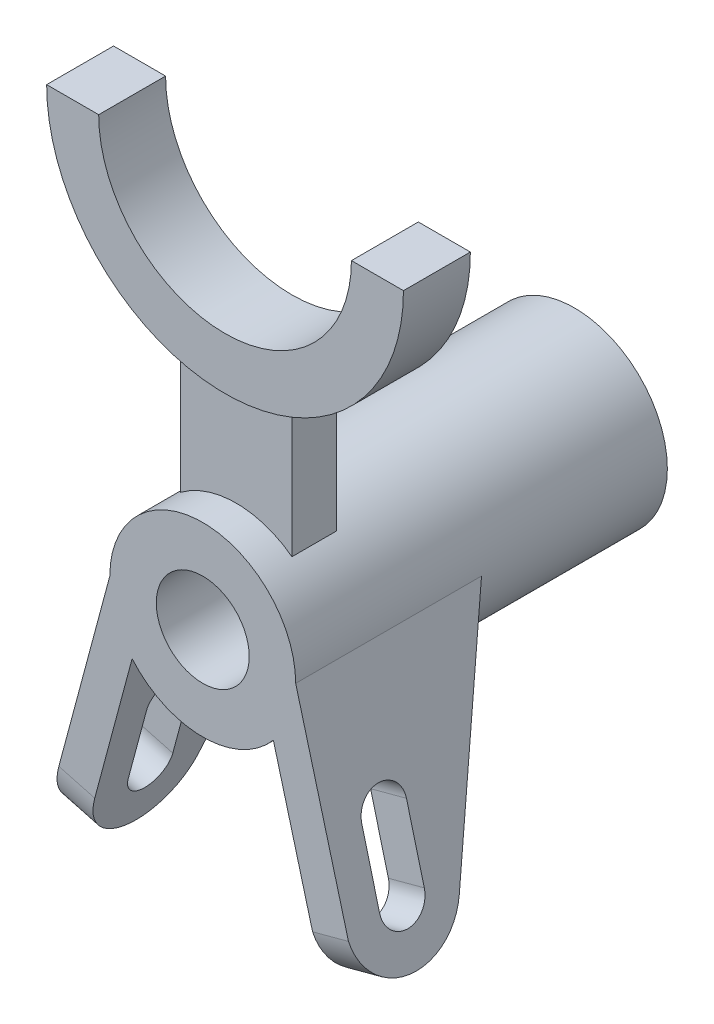
SolidWorks part; units mm, degrees
note: The reader was unsure of these and kept them because the rebuilt part matched: shared geometry of "Sketch1<3>", "Sketch1<4>", "Sketch1<5>", "Sketch1<6>".
material "텅스텐"
ref_plane "정면" through (0, 0, 0) normal (0, 0, 1) x (1, 0, 0)
ref_plane "윗면" through (0, 0, 0) normal (0, 1, 0) x (1, 0, 0)
ref_plane "우측면" through (0, 0, 0) normal (1, 0, 0) x (0, 0, -1)
sketch "Sketch1" plane through (0, 0, 0) normal (0, 0, 1) x (1, 0, 0)
  line L0 (-48, 100) -> (-34, 100)
  line L1 (34, 100) -> (48, 100)
  line L2 (0, -80.5181) -> (0, 148.3277) construction
  line L5 (-15, 20) -> (-15, 57.4935)
  line L7 (15, 20) -> (15, 57.4935)
  line L8 (25, 0) -> (42.5997, -65.683)
  line L9 (42.5997, -65.683) -> (32.9404, -68.2711)
  line L10 (32.9404, -68.2711) -> (15.3407, -2.5882)
  line L11 (15.3407, -2.5882) -> (25, 0)
  line L12 (-32.9404, -68.2711) -> (-15.3407, -2.5882)
  line L13 (-42.5997, -65.683) -> (-32.9404, -68.2711)
  line L14 (-25, 0) -> (-42.5997, -65.683)
  line L15 (-15.3407, -2.5882) -> (-25, 0)
  circle A0 centre (0, 0) radius 25
  arc A1 (-48, 100) -> (48, 100) centre (0, 100) ccw
  arc A3 (-34, 100) -> (34, 100) centre (0, 100) ccw
  circle A4 centre (0, 100) radius 48 construction
  circle A5 centre (0, 100) radius 34 construction
  point P17 (-15.3407, 19.7398)
  point P28 (15.3407, 19.7398)
  dimension "D1" = 50
  dimension "D2" = 96
  dimension "D4" = 30
  dimension "D5" = 100
  dimension "D6" = 30
  dimension "D7" = 10
  dimension "D8" = 68
  dimension "D3" = 14
extrude "Boss-Extrude1" add sketch "Sketch1" along normal mid plane 18
extrude "Boss-Extrude2" add sketch "Sketch1<3>" along normal mid plane 12 contours A1 L5 A0 L7
sketch "Sketch1<3>" plane through (0, 0, 0) normal (0, 0, 1) x (1, 0, 0) same geometry as "Sketch1"
extrude "Boss-Extrude3" add sketch "Sketch1<4>" along normal blind 15 and the other way blind 85 contours L15 A0 L12 | L10 A0 L11 | L11 A0 L15 L12 L10
sketch "Sketch1<4>" plane through (0, 0, 0) normal (0, 0, 1) x (1, 0, 0) same geometry as "Sketch1"
extrude "Boss-Extrude4" add sketch "Sketch1<5>" along normal blind 15 and the other way blind 35 contours A0 L14 L13 L12 | A0 L10 L9 L8
sketch "Sketch1<5>" plane through (0, 0, 0) normal (0, 0, 1) x (1, 0, 0) same geometry as "Sketch1"
sketch "Sketch3" plane through (-23.3253, 6.25, 0) normal (-0.9659, 0.2588, 0) x (0, 0, 1)
  line L0 (-35, -6.4705) -> (15, -6.4705)
  line L1 (15, -6.4705) -> (15, -59.4705)
  line L2 (15, -6.4705) -> (15, -74.4705) construction
  line L3 (-14.115, -64.5464) -> (-35, -6.4705)
  line L4 (0, -59.4705) -> (0, -40.4705) construction
  line L5 (0, -57.4193) -> (0, 1.4705) construction
  line L6 (-6, -59.4705) -> (-6, -40.4705)
  line L7 (6, -59.4705) -> (6, -40.4705)
  line L9 (-35, -6.4705) -> (15, -6.4705)
  line L10 (-35, -6.4705) -> (-35, -74.4705)
  line L11 (-35, -74.4705) -> (15, -74.4705)
  line L12 (15, -6.4705) -> (15, -74.4705)
  arc A0 (15, -59.4705) -> (-14.115, -64.5464) centre (0, -59.4705) cw
  arc A1 (-6, -59.4705) -> (6, -59.4705) centre (0, -59.4705) ccw
  arc A2 (6, -40.4705) -> (-6, -40.4705) centre (0, -40.4705) ccw
  point P9 (0, -49.9705)
  dimension "D1" = 15
  dimension "D3" = 6
  dimension "D2" = 68
  dimension "D4" = 19
extrude "Cut-Extrude1" cut sketch "Sketch3" against normal blind 10
sketch "Sketch4" plane through (23.3253, 6.25, 0) normal (0.9659, 0.2588, 0) x (0, 0, -1)
  line L0 (-15, -6.4705) -> (35, -6.4705)
  line L1 (35, -6.4705) -> (13.9863, -64.5721)
  line L2 (-15, -6.4705) -> (-15, -74.4705) construction
  line L3 (-15, -61.3597) -> (-15, -6.4705)
  line L4 (-0.1195, -59.4705) -> (0, -40.4705) construction
  line L5 (0, 6.4705) -> (0, -52.4193) construction
  line L6 (-6.1193, -59.4328) -> (-5.9999, -40.4328)
  line L7 (5.8804, -59.5082) -> (5.9999, -40.5082)
  line L9 (-15, -74.4705) -> (35, -74.4705)
  line L10 (-15, -74.4705) -> (-15, -6.4705)
  line L11 (-15, -6.4705) -> (35, -6.4705)
  line L12 (35, -74.4705) -> (35, -6.4705)
  arc A0 (13.9863, -64.5721) -> (-15, -61.3597) centre (-0.1195, -59.4705) cw
  arc A1 (-6.1193, -59.4328) -> (5.8804, -59.5082) centre (-0.1195, -59.4705) ccw
  arc A2 (5.9999, -40.5082) -> (-5.9999, -40.4328) centre (0, -40.4705) ccw
  point P9 (-0.0597, -49.9705)
  dimension "D2" = 15
  dimension "D3" = 6
  dimension "D1" = 68
  dimension "D4" = 19
extrude "Cut-Extrude2" cut sketch "Sketch4" against normal blind 10
extrude "Boss-Extrude6" add sketch "Sketch1<6>" along normal blind 15 and the other way blind 85 contours A0
sketch "Sketch1<6>" plane through (0, 0, 0) normal (0, 0, 1) x (1, 0, 0) same geometry as "Sketch1"
hole_wizard "Ø25.0 (25) Diameter Hole1" positions "Sketch8" profile "Sketch9" hole size "Ø25.0" standard "Ansi Metric" end condition up to next
sketch "Sketch8" plane through (0, 0, -85) normal (0, 0, -1) x (-1, 0, 0)
  point P0 (0, 0)
sketch "Sketch9" plane through (0, 0, -85) normal (1, 0, 0) x (0, 1, 0)
  line L0 (0, 0) -> (0, 100)
  line L1 (0, 100) -> (12.5, 100)
  line L2 (12.5, 100) -> (12.5, 0)
  line L5 (12.5, 0) -> (0, 0)
  line L11 (0, -6.35) -> (0, 107.95) construction
  dimension "관통 구멍 지름" = 25
  dimension "관통 구멍 깊이" = 100
